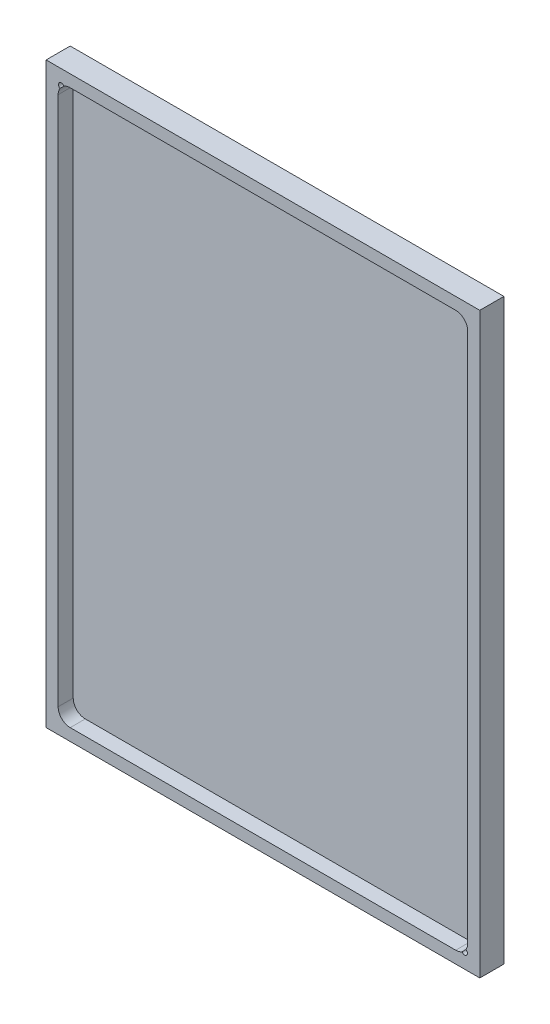
SolidWorks part; units mm, degrees
material "AISI 304"
ref_plane "Front Plane" through (0, 0, 0) normal (0, 0, 1) x (1, 0, 0)
ref_plane "Top Plane" through (0, 0, 0) normal (0, 1, 0) x (1, 0, 0)
ref_plane "Right Plane" through (0, 0, 0) normal (1, 0, 0) x (0, 0, -1)
sketch "Sketch1" plane through (0, 0, 0) normal (0, 0, 1) x (1, 0, 0)
  line L1 (114.3, -152.4) -> (-114.3, -152.4)
  line L2 (114.3, -152.4) -> (114.3, 152.4)
  line L3 (114.3, 152.4) -> (-114.3, 152.4)
  line L4 (-114.3, -152.4) -> (-114.3, 152.4)
  line L5 (114.3, -152.4) -> (-114.3, 152.4) construction
  line L6 (114.3, 152.4) -> (-114.3, -152.4) construction
  point P0 (0, 0)
  dimension "D1" = 228.6
  dimension "D2" = 304.8
extrude "Boss-Extrude1" add sketch "Sketch1" along normal blind 12.7
sketch "Sketch2" plane through (0, 0, 12.7) normal (0, 0, 1) x (1, 0, 0)
  line L0 (-114.3, 152.4) -> (-114.3, -152.4) construction
  line L1 (101.6, -146.05) -> (-101.6, -146.05)
  line L2 (107.95, -139.7) -> (107.95, 139.7)
  line L3 (101.6, 146.05) -> (-101.6, 146.05)
  line L4 (-107.95, -139.7) -> (-107.95, 139.7)
  line L5 (107.95, -146.05) -> (-107.95, 146.05) construction
  line L6 (107.95, 146.05) -> (-107.95, -146.05) construction
  line L7 (114.3, 152.4) -> (-114.3, 152.4) construction
  arc A0 (-101.6, -146.05) -> (-107.95, -139.7) centre (-101.6, -139.7) cw
  arc A1 (101.6, -146.05) -> (107.95, -139.7) centre (101.6, -139.7) ccw
  arc A2 (107.95, 139.7) -> (101.6, 146.05) centre (101.6, 139.7) ccw
  arc A3 (-101.6, 146.05) -> (-107.95, 139.7) centre (-101.6, 139.7) ccw
  point P0 (0, 0)
  dimension "D3" = 6.35
  dimension "D1" = 6.35
  dimension "D2" = 6.35
extrude "Cut-Extrude1" cut sketch "Sketch2" against normal blind 7.9375
hole_wizard "Ø3.0 (3) Diameter Hole1" positions "Sketch3" profile "Sketch4" hole size "Ø3.0" standard "ANSI Metric"
sketch "Sketch3" plane through (0, 0, 12.7) normal (0, 0, 1) x (1, 0, 0)
  line L0 (-114.3, -152.4) -> (114.3, -152.4) construction
  line L1 (114.3, -152.4) -> (114.3, 152.4) construction
  line L2 (-114.3, 152.4) -> (-114.3, -152.4) construction
  line L4 (114.3, 152.4) -> (-114.3, 152.4) construction
  point P0 (-106.3, 144.4)
  point P2 (106.3, -144.4)
  dimension "D1" = 8
  dimension "D2" = 8
  dimension "D3" = 8
  dimension "D4" = 8
sketch "Sketch4" plane through (-106.3, 144.4, 12.7) normal (1, 0, 0) x (0, -1, 0)
  line L0 (0, 0) -> (0, 5.9013)
  line L1 (0, 5.9013) -> (1.5, 5)
  line L2 (1.5, 5) -> (1.5, 0)
  line L5 (1.5, 0) -> (0, 0)
  line L10 (0, 5.9013) -> (-1.5, 5) construction
  line L11 (0, -6.35) -> (0, 107.95) construction
  dimension "Hole Dia." = 3
  dimension "Hole Depth" = 5
  dimension "Drill Angle" = 118
